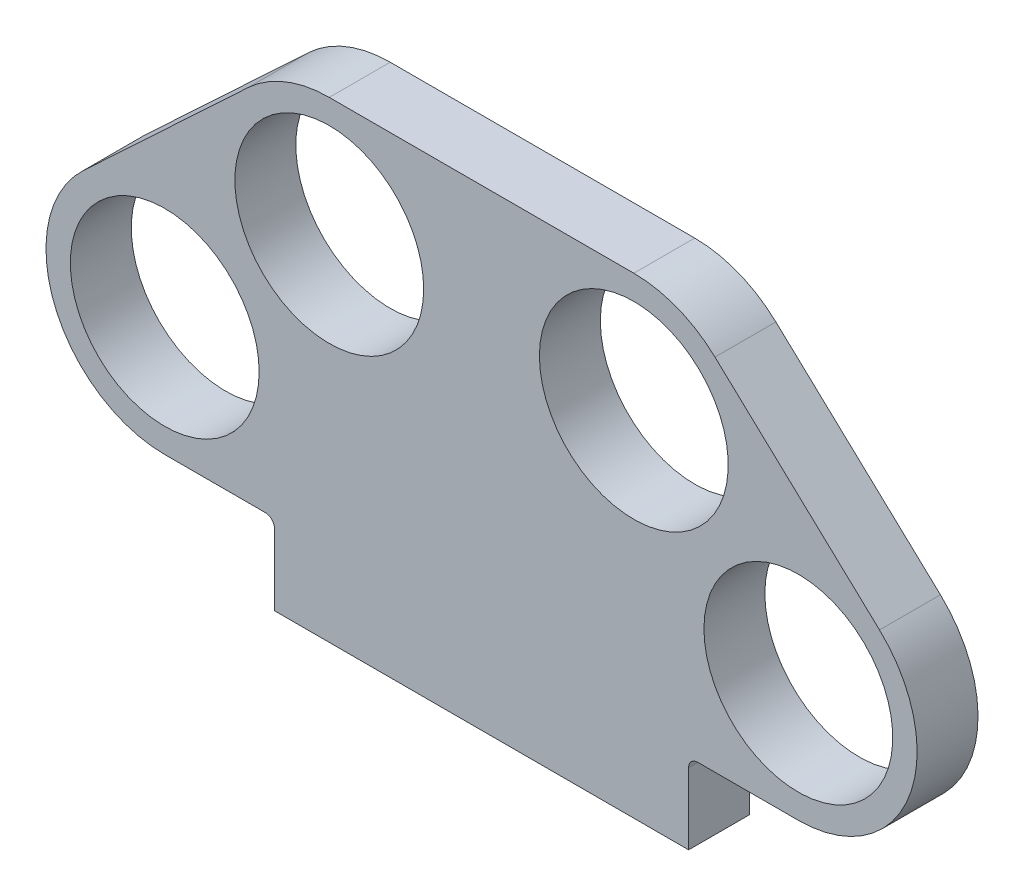
SolidWorks part; units mm, degrees
ref_plane "Front Plane" through (0, 0, 0) normal (0, 0, 1) x (1, 0, 0)
ref_plane "Top Plane" through (0, 0, 0) normal (0, 1, 0) x (1, 0, 0)
ref_plane "Right Plane" through (0, 0, 0) normal (1, 0, 0) x (0, 0, -1)
sketch "Sketch1" plane through (0, 0, 0) normal (0, 0, 1) x (1, 0, 0)
  line L0 (-11.9595, 12.7758) -> (-50.7466, -23.5332) construction
  line L1 (11.9595, 12.7758) -> (50.7466, -23.5332) construction
  line L2 (-11.9595, 12.7758) -> (11.9595, 12.7758) construction
  line L3 (-50.7466, -23.5332) -> (50.7466, -23.5332) construction
  line L4 (-17.5, -2) -> (17.5, -2) construction
  line L5 (0, 0) -> (0, -2) construction
  line L6 (-17.5, -2) -> (-17.5, 4) construction
  line L7 (-17.5, 4) -> (-20.5, 4) construction
  line L8 (-20.5, 4) -> (-20.5, -5) construction
  line L9 (-20.5, -5) -> (20.5, -5) construction
  line L10 (20.5, -5) -> (20.5, 4) construction
  line L11 (20.5, 4) -> (17.5, 4) construction
  line L12 (17.5, 4) -> (17.5, -2) construction
  line L13 (0, -2) -> (0, 40.1846) construction
  line L14 (-26.0058, 14.352) -> (-12.5, 26.995) construction
  line L15 (-32.669, 21.47) -> (-19.1632, 34.1129)
  line L16 (-26.0058, 4.602) -> (-17.75, 4.602)
  line L17 (-17, 3.852) -> (-17, -2)
  line L18 (-17, -2) -> (0, -2)
  line L19 (-12.5, 36.745) -> (0, 36.745)
  line L20 (0, 36.745) -> (0, -2)
  circle A0 centre (0, 0) radius 17.5 construction
  circle A1 centre (-26.0058, 14.352) radius 7.75
  circle A2 centre (-12.5, 26.995) radius 7.75
  circle A3 centre (-12.5, 26.995) radius 9.75 construction
  circle A4 centre (-26.0058, 14.352) radius 9.75 construction
  arc A5 (-17.75, 4.602) -> (-17, 3.852) centre (-17.75, 3.852) cw
  arc A6 (-19.1632, 34.1129) -> (-12.5, 36.745) centre (-12.5, 26.995) cw
  arc A7 (-26.0058, 4.602) -> (-32.669, 21.47) centre (-26.0058, 14.352) cw
  dimension "D1" = 35
  dimension "D8" = 15.5
  dimension "D10" = 3
  dimension "D11" = 2
  dimension "D13" = 0.75
  dimension "D2" = 93.78
  dimension "D3" = 35
  dimension "2" = 2
  dimension "D4" = 6
  dimension "D5" = 3
  dimension "D6" = 3
  dimension "D7" = 3
  dimension "D9" = 25
  dimension "D12" = 0.5
extrude "Boss-Extrude1" add sketch "Sketch1" along normal blind 5 contours A7 L16 A5 L17 L18 L20 L19 A6 L15 A2 A1 region at (-12.1141, 15.2891, 0)
mirror "Mirror1" about plane through (0, 0, 0) normal (1, 0, 0) of "Boss-Extrude1"
